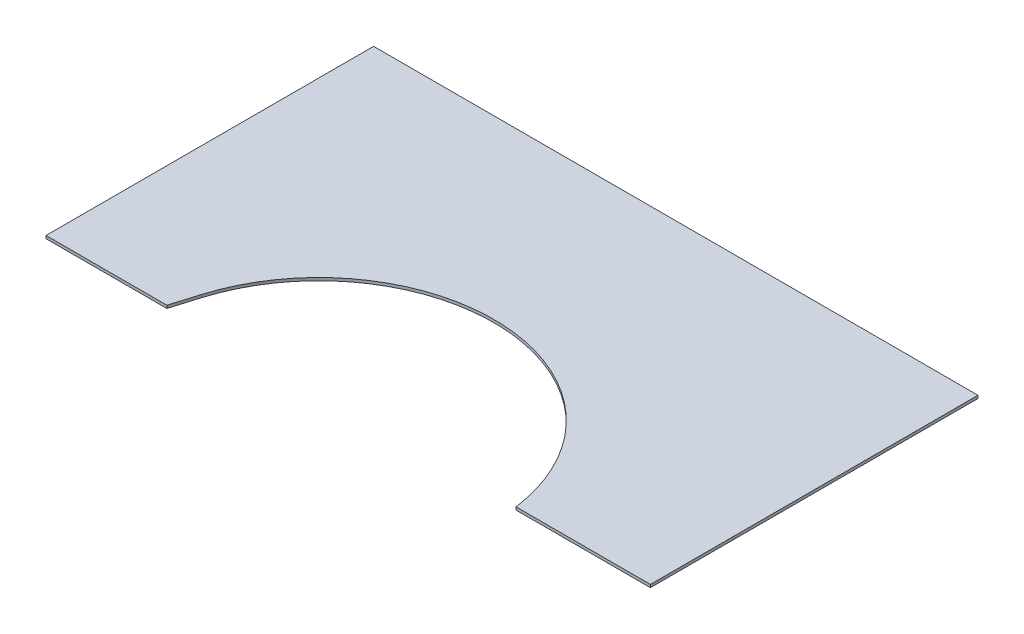
SolidWorks part; units mm, degrees
ref_plane "Front Plane" through (0, 0, 0) normal (0, 0, 1) x (1, 0, 0)
ref_plane "Top Plane" through (0, 0, 0) normal (0, 1, 0) x (1, 0, 0)
ref_plane "Right Plane" through (0, 0, 0) normal (1, 0, 0) x (0, 0, -1)
sketch "Sketch1" plane through (0, 0, 0) normal (0, 1, 0) x (1, 0, 0)
  line L0 (0, 368.3) -> (679.45, 368.3)
  line L1 (0, 0) -> (679.45, 0)
  line L2 (0, 0) -> (0, 368.3)
  line L4 (679.45, 0) -> (679.45, 368.3)
  point P7 (679.45, 368.3)
  dimension "D1" = 368.3
  dimension "D2" = 679.45
extrude "Boss-Extrude1" add sketch "Sketch1" along normal blind 3.175
sketch "Sketch2" plane through (0, 3.175, 0) normal (0, 1, 0) x (1, 0, 0)
  line L12 (135.833, 0) -> (144.9434, 30.1431)
  line L13 (0, 0) -> (679.45, 0) construction
  line L14 (135.833, 0) -> (488.6676, 0)
  arc A8 (494.6251, -139.7168) -> (530.1226, -33.1583) centre (333.375, -26.8083) ccw construction
  arc A10 (327.025, 169.9393) -> (144.9434, 30.1431) centre (333.375, -26.8083) ccw construction
  arc A11 (530.1226, -33.1583) -> (327.025, 169.9393) centre (333.375, -26.8083) ccw construction
  arc A12 (494.6251, -139.7168) -> (530.1226, -33.1583) centre (333.375, -26.8083) ccw
  arc A14 (327.025, 169.9393) -> (144.9434, 30.1431) centre (333.375, -26.8083) ccw
  arc A15 (530.1226, -33.1583) -> (327.025, 169.9393) centre (333.375, -26.8083) ccw
  spline S0 degree 3 poles (579.0964, 856.7076) (461.012, 14.849) (536.0415, -102.4122) (484.7792, -150.2338) (475.3357, -156.2316) (461.5217, -161.4443) (336.0356, -185.9928) (128.9981, -11.9673) (1337.1517, 258.4834) knots -0.818542 -0.818542 -0.818542 -0.818542 0.027722 0.055445 0.110889 0.166334 0.221779 1.450191 1.450191 1.450191 1.450191 only from (494.6251, -139.7168) to (431.2444, -164.9838) construction
  spline S1 degree 3 poles (494.6251, -139.7168) (493.4573, -141.3846) (490.8952, -144.5283) (484.7792, -150.2338) (475.3357, -156.2316) (461.5217, -161.4443) (379.6484, -177.461) (267.7224, -112.1878) (488.6676, 0) knots 0 0 0 0 0.027722 0.055445 0.110889 0.166334 0.221779 0.984715 0.984715 0.984715 0.984715
  dimension "D1" = 196.85
extrude "Cut-Extrude1" cut sketch "Sketch2" against normal through all
